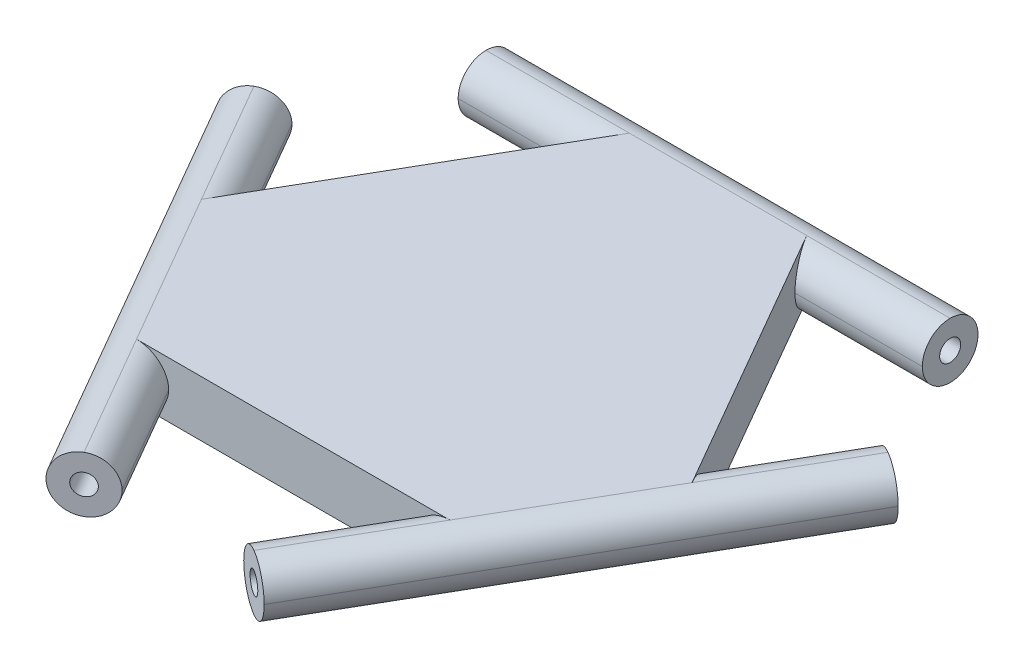
SolidWorks part; units mm, degrees
ref_plane "Front Plane" through (0, 0, 0) normal (0, 0, 1) x (1, 0, 0)
ref_plane "Top Plane" through (0, 0, 0) normal (0, 1, 0) x (1, 0, 0)
ref_plane "Right Plane" through (0, 0, 0) normal (1, 0, 0) x (0, 0, -1)
sketch "Sketch1" plane through (0, 0, 0) normal (0, 1, 0) x (1, 0, 0)
  line L0 (-24.695, -1.2271) -> (-11.2848, 22)
  line L1 (11.2848, 22) -> (25, 22)
  line L2 (13.4101, -20.7729) -> (-13.4101, -20.7729)
  line L3 (11.2848, 22) -> (24.695, -1.2271)
  line L4 (-25, 22) -> (-11.2848, 22)
  line L5 (-25, 22) -> (-25, 28)
  line L6 (-25, 28) -> (25, 28)
  line L7 (25, 22) -> (25, 28)
  line L8 (-25, 22) -> (25, 28) construction
  line L9 (-25, 28) -> (25, 22) construction
  line L10 (36.7487, 7.6506) -> (11.7487, -35.6506)
  line L11 (31.5526, 10.6506) -> (36.7487, 7.6506)
  line L12 (31.5526, 10.6506) -> (24.695, -1.2271)
  line L13 (13.4101, -20.7729) -> (6.5526, -32.6506)
  line L14 (6.5526, -32.6506) -> (11.7487, -35.6506)
  line L15 (-11.7487, -35.6506) -> (-36.7487, 7.6506)
  line L16 (-6.5526, -32.6506) -> (-11.7487, -35.6506)
  line L17 (-6.5526, -32.6506) -> (-13.4101, -20.7729)
  line L18 (-24.695, -1.2271) -> (-31.5526, 10.6506)
  line L19 (-31.5526, 10.6506) -> (-36.7487, 7.6506)
  circle A0 centre (0, 0) radius 20.7729 construction
  point P3 (0, 0)
  point P5 (0, 25)
  point P27 (0, 0)
  dimension "D5" = 41.5459
  dimension "D2" = 50
  dimension "D3" = 6
  dimension "D4" = 25
  dimension "D1" = 3
extrude "Boss-Extrude1" add sketch "Sketch1" along normal blind 6
fillet "Fillet3" radius 3 18 edges at (24.2487, 0, 14) (24.2487, 6, 14) (0, 0, -28) (0, 6, -28) (-24.2487, 0, 14) (-24.2487, 6, 14) (9.9814, 0, 26.7118) (9.9814, 6, 26.7118) (28.1238, 0, -4.7118) (28.1238, 6, -4.7118) (18.1424, 0, -22) (18.1424, 6, -22) (-18.1424, 6, -22) (-18.1424, 0, -22) (-28.1238, 6, -4.7118) (-28.1238, 0, -4.7118) (-9.9814, 0, 26.7118) (-9.9814, 6, 26.7118)
hole_wizard "#4-40 Tapped Hole1" positions "Sketch3" profile "Sketch2" tap size "#4-40" standard "ANSI Inch" end condition through all
sketch "Sketch3" plane through (12.5, 0, 21.6506) normal (0.5, 0, 0.866) x (0.866, 0, -0.5)
  point P0 (-25, 3)
sketch "Sketch2" plane through (-9.1506, 3, 34.1506) normal (0, 1, 0) x (0.866, 0, -0.5)
  line L0 (0, 0) -> (0, 67.6231)
  line L1 (0, 67.6231) -> (1.1303, 67.6231)
  line L2 (1.1303, 67.6231) -> (1.1303, 0)
  line L5 (1.1303, 0) -> (0, 0)
  line L11 (0, -6.35) -> (0, 107.95) construction
  dimension "Thru Tap Drill Dia." = 2.2606
  dimension "Thru Tap Drill Depth" = 67.6231
cosmetic thread "Hole Thread1" parameters "D2"=2.8448
hole_wizard "#4-40 Tapped Hole2" positions "Sketch5" profile "Sketch4" tap size "#4-40" standard "ANSI Inch" end condition through all
sketch "Sketch5" plane through (12.5, 0, -21.6506) normal (0.5, 0, -0.866) x (-0.866, 0, -0.5)
  point P0 (-25, 3)
sketch "Sketch4" plane through (34.1506, 3, -9.1506) normal (0, 1, 0) x (-0.866, 0, -0.5)
  line L0 (0, 0) -> (0, 74.2487)
  line L1 (0, 74.2487) -> (1.1303, 74.2487)
  line L2 (1.1303, 74.2487) -> (1.1303, 0)
  line L5 (1.1303, 0) -> (0, 0)
  line L11 (0, -6.35) -> (0, 107.95) construction
  dimension "Thru Tap Drill Dia." = 2.2606
  dimension "Thru Tap Drill Depth" = 74.2487
cosmetic thread "Hole Thread2" parameters "D2"=2.8448
hole_wizard "#4-40 Tapped Hole3" positions "Sketch7" profile "Sketch6" tap size "#4-40" standard "ANSI Inch" end condition through all
sketch "Sketch7" plane through (-25, 0, 0) normal (-1, 0, 0) x (0, 0, 1)
  point P0 (-25, 3)
sketch "Sketch6" plane through (-25, 3, -25) normal (0, 1, 0) x (0, 0, 1)
  line L0 (0, 0) -> (0, 61.7487)
  line L1 (0, 61.7487) -> (1.1303, 61.7487)
  line L2 (1.1303, 61.7487) -> (1.1303, 0)
  line L5 (1.1303, 0) -> (0, 0)
  line L11 (0, -6.35) -> (0, 107.95) construction
  dimension "Thru Tap Drill Dia." = 2.2606
  dimension "Thru Tap Drill Depth" = 61.7487
cosmetic thread "Hole Thread3" parameters "D2"=2.8448
